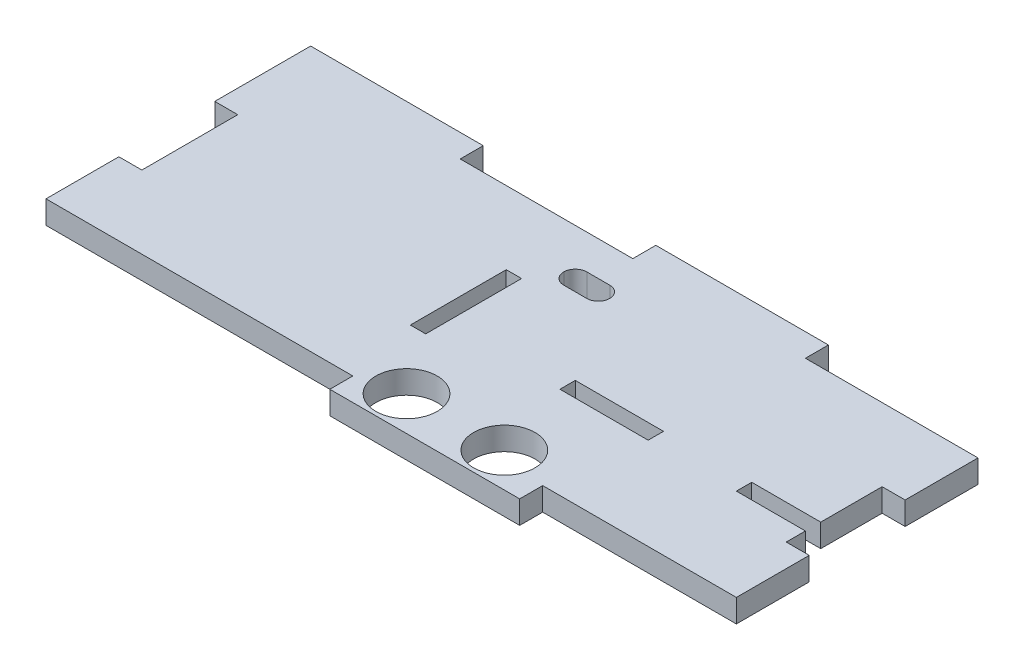
SolidWorks part; units mm, degrees
ref_plane "Front" through (0, 0, 0) normal (0, 0, 1) x (1, 0, 0)
ref_plane "Top" through (0, 0, 0) normal (0, 1, 0) x (1, 0, 0)
ref_plane "Right" through (0, 0, 0) normal (1, 0, 0) x (0, 0, -1)
sketch "Sketch1" plane through (0, 0, 0) normal (0, 1, 0) x (1, 0, 0)
  line L1 (0, 0) -> (180, 0)
  line L2 (0, 0) -> (0, 75)
  line L3 (0, 75) -> (180, 75)
  line L4 (180, 0) -> (180, 75)
  dimension "D1" = 180
  dimension "D2" = 75
extrude "Boss-Extrude1" add sketch "Sketch1" along normal blind 6
sketch "Sketch2" plane through (0, 6, 0) normal (0, 1, 0) x (1, 0, 0)
  line L0 (0, 0) -> (180, 0) construction
  line L5 (180, 0) -> (180, 75) construction
  line L6 (180, 34) -> (156, 34)
  line L7 (180, 34) -> (180, 30)
  line L8 (180, 30) -> (156, 30)
  line L9 (156, 34) -> (156, 30)
  line L10 (180, 75) -> (0, 75) construction
  line L11 (156, 34) -> (133, 34)
  line L12 (156, 34) -> (156, 30)
  line L13 (156, 30) -> (133, 30)
  line L14 (133, 34) -> (133, 30)
  line L15 (133, 34) -> (110, 34)
  line L16 (133, 34) -> (133, 30)
  line L17 (133, 30) -> (110, 30)
  line L18 (110, 34) -> (110, 30)
  line L19 (76, 75) -> (80, 75)
  line L20 (76, 75) -> (76, 50)
  line L21 (76, 50) -> (80, 50)
  line L22 (80, 75) -> (80, 50)
  line L23 (0, 75) -> (0, 0) construction
  line L24 (76, 50) -> (80, 50)
  line L25 (76, 50) -> (76, 25)
  line L26 (76, 25) -> (80, 25)
  line L27 (80, 50) -> (80, 25)
  line L28 (76, 25) -> (80, 25)
  line L29 (76, 25) -> (76, 0)
  line L30 (76, 0) -> (80, 0)
  line L31 (80, 25) -> (80, 0)
  line M9 (180, 0) -> (180, 75)
  dimension "D1" = 4
  dimension "D2" = 24
  dimension "D3" = 23
  dimension "D4" = 23
  dimension "D5" = 30
  dimension "D6" = 4
  dimension "D7" = 25
  dimension "D8" = 76
extrude "Cut-Extrude1" cut sketch "Sketch2" against normal blind 6 contours L15 L18 L17 L14 | L6 L9 L8 M9 | L25 L24 L27 L26
sketch "Sketch3" plane through (0, 6, 0) normal (0, 1, 0) x (1, 0, 0)
  line L0 (0, 0) -> (180, 0) construction
  line L1 (0, 75) -> (0, 0) construction
  line L3 (84, 60) -> (96, 60)
  line L4 (84, 60) -> (84, 54)
  line L5 (84, 54) -> (96, 54)
  line L6 (96, 60) -> (96, 54)
  line L7 (180, 75) -> (0, 75) construction
  circle A0 centre (91, 9) radius 8
  circle A1 centre (116.5, 9) radius 8
  dimension "D1" = 16
  dimension "D2" = 25.5
  dimension "D3" = 9
  dimension "D4" = 91
  dimension "D5" = 6
  dimension "D6" = 12
  dimension "D7" = 84
  dimension "D8" = 15
extrude "Cut-Extrude5" cut sketch "Sketch3" against normal through all
fillet "Fillet1" radius 3 4 edges at (96, 3, -54) (96, 3, -60) (84, 3, -54) (84, 3, -60)
sketch "Sketch4" plane through (0, 6, 0) normal (0, 1, 0) x (1, 0, 0)
  line L0 (180, 0) -> (180, 30) construction
  line L1 (0, 0) -> (80, 0)
  line L2 (0, 0) -> (0, 6)
  line L3 (0, 6) -> (80, 6)
  line L4 (80, 0) -> (80, 6)
  line L5 (180, 0) -> (129.5, 0)
  line L6 (180, 0) -> (180, 6)
  line L7 (180, 6) -> (129.5, 6)
  line L8 (129.5, 0) -> (129.5, 6)
  line L9 (180, 75) -> (174, 75)
  line L10 (180, 75) -> (180, 50)
  line L11 (180, 50) -> (174, 50)
  line L12 (174, 75) -> (174, 50)
  line L13 (174, 50) -> (180, 50)
  line L14 (174, 50) -> (174, 25)
  line L15 (174, 25) -> (180, 25)
  line L16 (180, 50) -> (180, 25)
  line L18 (174, 25) -> (180, 25)
  line L19 (174, 25) -> (174, 0)
  line L20 (174, 0) -> (180, 0)
  line L21 (180, 25) -> (180, 0)
  line L22 (0, 75) -> (6, 75)
  line L23 (0, 75) -> (0, 50)
  line L24 (0, 50) -> (6, 50)
  line L25 (6, 75) -> (6, 50)
  line L26 (0, 50) -> (6, 50)
  line L27 (0, 50) -> (0, 25)
  line L28 (0, 25) -> (6, 25)
  line L29 (6, 50) -> (6, 25)
  line L30 (0, 25) -> (6, 25)
  line L31 (0, 25) -> (0, 0)
  line L32 (0, 0) -> (6, 0)
  line L33 (6, 25) -> (6, 0)
  line L34 (0, 75) -> (45, 75)
  line L35 (0, 75) -> (0, 69)
  line L36 (0, 69) -> (45, 69)
  line L37 (45, 75) -> (45, 69)
  line L38 (45, 75) -> (90, 75)
  line L39 (45, 75) -> (45, 69)
  line L40 (45, 69) -> (90, 69)
  line L41 (90, 75) -> (90, 69)
  line L42 (90, 75) -> (135, 75)
  line L43 (90, 75) -> (90, 69)
  line L44 (90, 69) -> (135, 69)
  line L45 (135, 75) -> (135, 69)
  line L46 (135, 75) -> (180, 75)
  line L47 (135, 75) -> (135, 69)
  line L48 (135, 69) -> (180, 69)
  line L49 (180, 75) -> (180, 69)
  line M20 (156, 34) -> (180, 34)
  line M21 (180, 34) -> (180, 75)
  line M23 (0, 75) -> (0, 0)
  line M24 (0, 0) -> (180, 0)
  line M25 (180, 0) -> (180, 30)
  line M26 (180, 30) -> (156, 30)
  dimension "D1" = 6
  dimension "D2" = 6
  dimension "D3" = 80
  dimension "D4" = 49.5
  dimension "D5" = 6
extrude "Cut-Extrude6" cut sketch "Sketch4" against normal through all contours L19 L7 L8 M24 | L7 L19 L5 M25 | L14 L15 M25 M26 | L11 L14 M20 M21 | L29 L24 L28 M23 | L33 L3 M23 M24 | L3 L33 L1 L4 | L47 L46 L49 L48 | L39 L38 L41 L40
